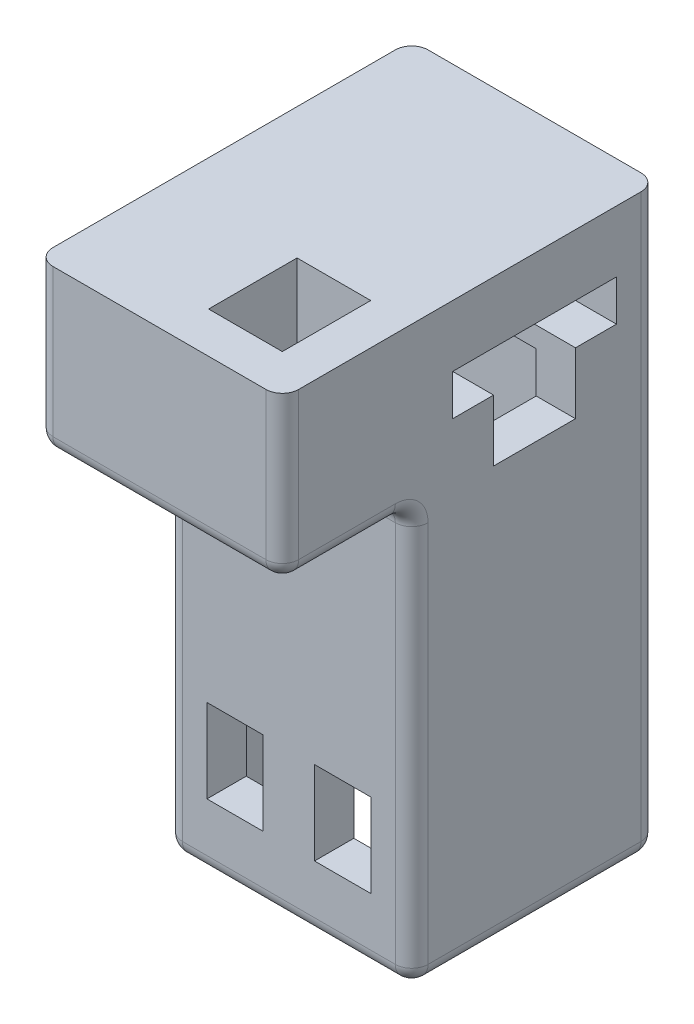
SolidWorks part; units mm, degrees
ref_plane "Front Plane" through (0, 0, 0) normal (0, 0, 1) x (1, 0, 0)
ref_plane "Top Plane" through (0, 0, 0) normal (0, 1, 0) x (1, 0, 0)
ref_plane "Right Plane" through (0, 0, 0) normal (1, 0, 0) x (0, 0, -1)
sketch "Sketch1" plane through (0, 0, 0) normal (0, 1, 0) x (1, 0, 0)
  line L1 (-19.05, -19.05) -> (19.05, -19.05)
  line L2 (-19.05, -19.05) -> (-19.05, 19.05)
  line L3 (-19.05, 19.05) -> (19.05, 19.05)
  line L4 (19.05, -19.05) -> (19.05, 19.05)
  line L5 (-19.05, -19.05) -> (19.05, 19.05) construction
  line L6 (-19.05, 19.05) -> (19.05, -19.05) construction
  line L7 (12.954, -12.954) -> (-12.954, -12.954)
  line L8 (12.954, -12.954) -> (12.954, 12.954)
  line L9 (12.954, 12.954) -> (-12.954, 12.954)
  line L10 (-12.954, -12.954) -> (-12.954, 12.954)
  line L11 (12.954, -12.954) -> (-12.954, 12.954) construction
  line L12 (12.954, 12.954) -> (-12.954, -12.954) construction
  point P0 (0, 0)
  point P6 (0, 0)
  dimension "D1" = 38.1
  dimension "D2" = 38.1
  dimension "D3" = 25.908
extrude "Boss-Extrude1" add sketch "Sketch1" along normal blind 64.389 contours L3 L4 L1 L2
ref_plane "Plane1" through (0, 64.389, 0) normal (0, -1, 0) x (-1, 0, 0)
sketch "Sketch2" plane through (0, 0, 19.05) normal (0, 0, 1) x (1, 0, 0)
  line L0 (-19.05, 0) -> (19.05, 0) construction
  line L1 (-12.7, 23.114) -> (-3.9793, 23.114)
  line L2 (-12.7, 23.114) -> (-12.7, 10.16)
  line L3 (-12.7, 10.16) -> (-3.9793, 10.16)
  line L4 (-3.9793, 23.114) -> (-3.9793, 10.16)
  line L5 (-12.7, 23.114) -> (-3.9793, 10.16) construction
  line L6 (-12.7, 10.16) -> (-3.9793, 23.114) construction
  line L8 (0, -55) -> (0, 55) construction
  line L9 (3.9793, 23.114) -> (12.7, 23.114)
  line L10 (3.9793, 23.114) -> (3.9793, 10.16)
  line L11 (3.9793, 10.16) -> (12.7, 10.16)
  line L12 (12.7, 23.114) -> (12.7, 10.16)
  line L13 (3.9793, 23.114) -> (12.7, 10.16) construction
  line L14 (3.9793, 10.16) -> (12.7, 23.114) construction
  point P0 (-8.3397, 16.637)
  point P9 (8.3397, 16.637)
  point P14 (0, 0)
  dimension "D1" = 10.16
  dimension "D2" = 8.3397
  dimension "D3" = 8.7207
  dimension "D4" = 12.954
  dimension "D5" = 8.3397
extrude "Cut-Extrude1" cut sketch "Sketch2" against normal up to surface (38.1 mm away) contours L12 L9 L10 L11 | L4 L3 L2 L1 region at (8.3397, 16.637, 19.05) up to face at (0, 32.1945, -19.05)
sketch "Sketch3" plane through (0, 64.389, 0) normal (0, -1, 0) x (-1, 0, 0)
  line L1 (19.05, 19.05) -> (-19.05, 19.05)
  line L2 (19.05, 19.05) -> (19.05, -19.05)
  line L3 (19.05, -19.05) -> (-19.05, -19.05)
  line L4 (-19.05, 19.05) -> (-19.05, -19.05)
extrude "Boss-Extrude2" add sketch "Sketch3" against normal blind 25.4
extrude "Cut-Extrude2" cut sketch "Sketch1<3>" along normal offset from surface (70.739 mm away) 6.35 contours L10 L7 L8 L9 region at (0, 0, 0) up to plane "Plane1" offset beyond the face yes
sketch "Sketch1<3>" plane through (0, 0, 0) normal (0, 1, 0) x (1, 0, 0) same geometry as "Sketch1"
sketch "Sketch5" plane through (19.05, 0, 0) normal (1, 0, 0) x (0, 0, -1)
  line L0 (-12.7, 80.264) -> (12.7, 80.264)
  line L1 (12.7, 80.264) -> (12.7, 73.914)
  line L2 (12.7, 73.914) -> (6.35, 73.914)
  line L3 (6.35, 73.914) -> (6.35, 64.389)
  line L4 (6.35, 64.389) -> (-6.35, 64.389)
  line L5 (-6.35, 64.389) -> (-6.35, 73.914)
  line L6 (-6.35, 73.914) -> (-12.7, 73.914)
  line L7 (-12.7, 73.914) -> (-12.7, 80.264)
  line L8 (19.05, 64.389) -> (-19.05, 64.389) construction
  point P7 (37.3828, 92.8143)
  point P9 (0, 80.264)
  point P10 (0, 64.389)
  point P13 (0, 64.389)
  dimension "D1" = 25.4
  dimension "D2" = 6.35
  dimension "D3" = 9.525
  dimension "D4" = 12.7
extrude "Cut-Extrude4" cut sketch "Sketch5" against normal up to surface (32.004 mm away) up to face at (-12.954, 35.3695, 0)
sketch "Sketch7" plane through (0, 0, 19.05) normal (0, 0, 1) x (1, 0, 0)
  line L0 (19.05, 89.789) -> (19.05, 0) construction
  line L1 (-19.05, 89.789) -> (19.05, 89.789)
  line L2 (-19.05, 89.789) -> (-19.05, 64.389)
  line L3 (-19.05, 64.389) -> (19.05, 64.389)
  line L4 (19.05, 89.789) -> (19.05, 64.389)
  dimension "D1" = 25.4
extrude "Boss-Extrude3" add sketch "Sketch7" along normal blind 20.066
sketch "Sketch9" plane through (0, 89.789, 0) normal (0, 1, 0) x (1, 0, 0)
  line L0 (19.05, -39.116) -> (-19.05, -39.116) construction
  line L1 (1.27, -32.766) -> (12.7, -32.766)
  line L2 (1.27, -32.766) -> (1.27, -19.05)
  line L3 (1.27, -19.05) -> (12.7, -19.05)
  line L4 (12.7, -32.766) -> (12.7, -19.05)
  line L5 (19.05, 19.05) -> (19.05, -39.116) construction
  dimension "D1" = 6.35
  dimension "D2" = 11.43
  dimension "D3" = 13.716
  dimension "D4" = 6.35
extrude "Cut-Extrude5" cut sketch "Sketch9" against normal blind 21.59 contours L2 L3 L4 L1
fillet "Fillet1" radius 2.54 14 edges at (19.05, 0, 0) (0, 0, -19.05) (0, 0, 19.05) (-19.05, 0, 0) (0, 64.389, 19.05) (19.05, 32.1945, 19.05) (-19.05, 32.1945, 19.05) (-19.05, 64.389, 29.083) (0, 64.389, 39.116) (19.05, 64.389, 29.083) (19.05, 44.8945, -19.05) (-19.05, 44.8945, -19.05) (-19.05, 77.089, 39.116) (19.05, 77.089, 39.116)
